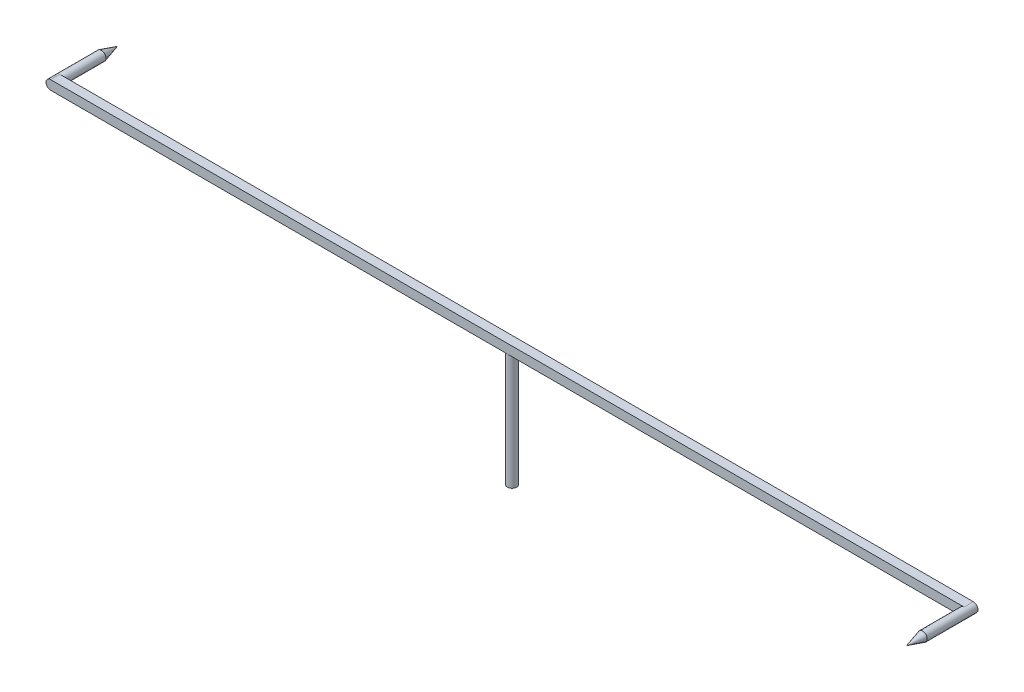
SolidWorks part; units mm, degrees
ref_plane "前视基准面" through (0, 0, 0) normal (0, 0, 1) x (1, 0, 0)
ref_plane "上视基准面" through (0, 0, 0) normal (0, 1, 0) x (1, 0, 0)
ref_plane "右视基准面" through (0, 0, 0) normal (1, 0, 0) x (0, 0, -1)
sketch "草图1" plane through (0, 0, 0) normal (0, 1, 0) x (1, 0, 0)
  circle A0 centre (0, 0) radius 0.4
  dimension "D1" = 0.8
extrude "凸台-拉伸1" add sketch "草图1" along normal blind 10
sketch "草图2" plane through (0, 10, 0) normal (0, 1, 0) x (1, 0, 0)
  line L1 (-40, 0.4) -> (40, 0.4)
  line L2 (-40, 0.4) -> (-40, -0.4)
  line L3 (-40, -0.4) -> (40, -0.4)
  line L4 (40, 0.4) -> (40, -0.4)
  circle A0 centre (0, 0) radius 0.4 construction
  dimension "D1" = 40
  dimension "D2" = 40
extrude "凸台-拉伸2" add sketch "草图2" along normal blind 0.8
fillet "圆角1" radius 0.4 4 edges at (40, 10, 0) (40, 10.8, 0) (-40, 10, 0) (-40, 10.8, 0)
sketch "草图3" plane through (0, 0, 0.4) normal (0, 0, 1) x (1, 0, 0)
  circle A0 centre (39.6, 10.4) radius 0.4
  dimension "D1" = 0.8
extrude "凸台-拉伸3" add sketch "草图3" along normal blind 3.6
sketch "草图4" plane through (0, 0, -0.4) normal (0, 0, -1) x (-1, 0, 0)
  circle A0 centre (39.6, 10.4) radius 0.4
  dimension "D1" = 0.8
extrude "凸台-拉伸4" add sketch "草图4" along normal blind 3.6
ref_plane "基准面1" through (0, 10.4, 0) normal (0, 1, 0) x (1, 0, 0)
sketch "草图5" plane through (0, 10.4, 0) normal (0, 1, 0) x (1, 0, 0)
  line L0 (39.6, -4) -> (39.6, -5.4)
  line L1 (39.2, -4) -> (40, -4) construction
  line L2 (40, -4) -> (39.6, -5.4)
  line L3 (39.6, -4) -> (40, -4)
  dimension "D1" = 1.4
revolve "旋转1" add sketch "草图5" angle 360 about L0
sketch "草图6" plane through (0, 10.4, 0) normal (0, 1, 0) x (1, 0, 0)
  line L0 (-39.6, 4) -> (-39.6, 5.4)
  line L1 (-39.2, 4) -> (-40, 4) construction
  line L2 (-39.6, 5.4) -> (-40, 4)
  line L3 (-40, 4) -> (-39.6, 4)
  dimension "D1" = 1.4
revolve "旋转2" add sketch "草图6" angle 360 about L0
